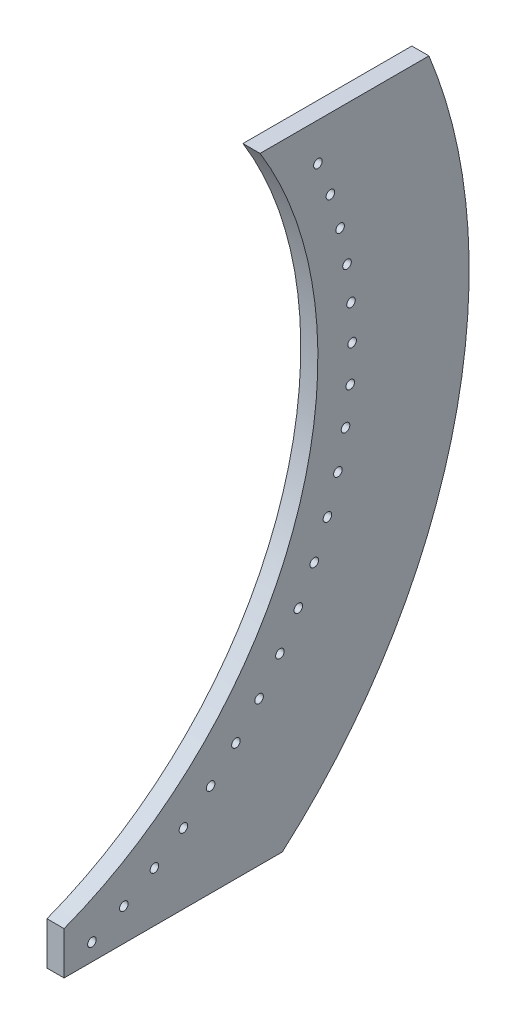
SolidWorks part; units mm, degrees
ref_plane "Front Plane" through (0, 0, 0) normal (0, 0, 1) x (1, 0, 0)
ref_plane "Top Plane" through (0, 0, 0) normal (0, 1, 0) x (1, 0, 0)
ref_plane "Right Plane" through (0, 0, 0) normal (1, 0, 0) x (0, 0, -1)
sketch "Sketch1" plane through (0, 0, 0) normal (1, 0, 0) x (0, 0, -1)
  line L0 (0, 609.6) -> (323.85, 609.6)
  line L1 (323.85, 609.6) -> (323.85, 0)
  line L2 (323.85, 0) -> (0, 0)
  line L3 (0, 609.6) -> (0, 577.85)
  line L4 (0, 0) -> (0, 31.75)
  arc A1 (0, 577.85) -> (0, 31.75) centre (-103.7599, 304.8) cw
  point P6 (0, 0)
  dimension "D4" = 292.1
  dimension "D1" = 609.6
  dimension "D2" = 323.85
  dimension "D3" = 546.1
extrude "Boss-Extrude1" add sketch "Sketch1" along normal blind 12.7
sketch "Sketch2" plane through (12.7, 0, 0) normal (1, 0, 0) x (0, 0, -1)
  line L0 (323.85, 0) -> (323.85, 609.6) construction
  line L1 (0, 609.6) -> (323.85, 609.6)
  line L2 (0, 609.6) -> (0, 457.2)
  line L3 (0, 457.2) -> (323.85, 457.2)
  line L4 (323.85, 609.6) -> (323.85, 457.2)
  dimension "D1" = 152.4
extrude "Cut-Extrude1" cut sketch "Sketch2" against normal blind 12.7
sketch "Sketch3" plane through (12.7, 0, 0) normal (1, 0, 0) x (0, 0, -1)
  circle A0 centre (-103.7599, 304.8) radius 317.5
  point P4 (-792.1279, -47.2619)
hole_wizard "1/4 (0.25) Diameter Hole2" positions "Sketch6" profile "Sketch7" hole size "1/4" standard "ANSI Inch" end condition through all
sketch "Sketch6" plane through (12.7, 0, 0) normal (1, 0, 0) x (0, 0, -1)
  line L0 (0, 0) -> (323.85, 0) construction
  point P0 (20.6742, 12.7)
  point P14 (44.3706, 23.9734)
  point P15 (67.0552, 37.165)
  point P16 (88.5729, 52.1849)
  point P17 (108.7768, 68.9305)
  point P18 (127.5288, 87.2872)
  point P19 (144.7009, 107.1298)
  point P20 (160.1757, 128.3227)
  point P21 (173.8477, 150.7211)
  point P22 (185.6232, 174.172)
  point P23 (195.422, 198.5152)
  point P24 (203.1771, 223.5844)
  point P25 (208.8355, 249.2085)
  point P26 (212.3585, 275.2123)
  point P27 (213.7221, 301.4182)
  point P28 (212.917, 327.6472)
  point P29 (209.9487, 353.7201)
  point P30 (204.8375, 379.4589)
  point P31 (197.6182, 404.6876)
  point P32 (188.3401, 429.2341)
  dimension "D1" = 12.7
  dimension "D2" = 317.5
  dimension "D3" = 20
sketch "Sketch7" plane through (12.7, 12.7, -20.6742) normal (0, 1, 0) x (0, 0, -1)
  line L0 (0, 0) -> (0, 12.7)
  line L1 (0, 12.7) -> (3.175, 12.7)
  line L2 (3.175, 12.7) -> (3.175, 0)
  line L5 (3.175, 0) -> (0, 0)
  line L11 (0, -6.35) -> (0, 107.95) construction
  dimension "Thru Hole Dia." = 6.35
  dimension "Thru Hole Depth" = 12.7
sketch "Sketch8" plane through (12.7, 0, 0) normal (1, 0, 0) x (0, 0, -1)
  line L0 (0, 0) -> (323.85, 0) construction
  line L1 (145.4321, 457.2) -> (323.85, 457.2) construction
  line L2 (270.7608, 457.2) -> (323.85, 457.2)
  line L3 (323.85, 457.2) -> (323.85, 0)
  line L4 (323.85, 0) -> (161.925, 0)
  arc A0 (161.925, 0) -> (270.7608, 457.2) centre (-103.7599, 304.8) ccw
extrude "Cut-Extrude2" cut sketch "Sketch8" against normal through all
